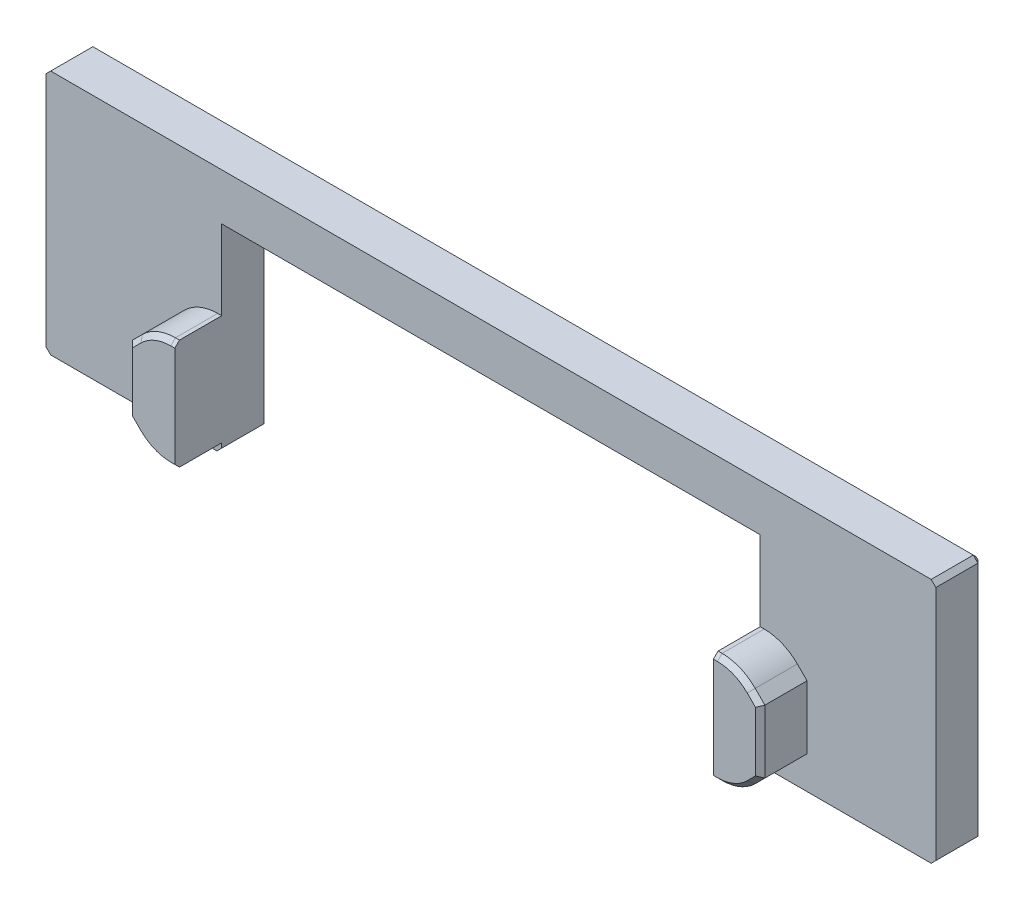
SolidWorks part; units mm, degrees
ref_plane "Front" through (0, 0, 0) normal (0, 0, 1) x (1, 0, 0)
ref_plane "Top" through (0, 0, 0) normal (0, 1, 0) x (1, 0, 0)
ref_plane "Right" through (0, 0, 0) normal (1, 0, 0) x (0, 0, -1)
sketch "Sketch1" plane through (0, 0, 0) normal (0, 0, 1) x (1, 0, 0)
  line L0 (-18.8, 5.25) -> (18.8, 5.25)
  line L5 (19, 5.05) -> (19, -5.05)
  line L6 (18.8, -5.25) -> (11.7, -5.25)
  line L7 (11.5, -5.05) -> (11.5, 3.25)
  line L8 (11.5, 3.25) -> (-11.5, 3.25)
  line L9 (-11.5, 3.25) -> (-11.5, -5.05)
  line L10 (-11.7, -5.25) -> (-18.8, -5.25)
  line L11 (-19, -5.05) -> (-19, 5.05)
  line L12 (19, 5.05) -> (19, -5.05) construction
  line L13 (18.8, -5.25) -> (11.7, -5.25) construction
  line L14 (18.8, 5.25) -> (-18.8, 5.25) construction
  line L15 (19, -5.05) -> (18.8, -5.25)
  line L16 (-11.7, -5.25) -> (-18.8, -5.25) construction
  line L17 (-19, 5.05) -> (-19, -5.05) construction
  line L18 (11.7, -5.25) -> (11.5, -5.05)
  line L19 (18.8, 5.25) -> (19, 5.05)
  line L20 (-19, 5.05) -> (-18.8, 5.25)
  line L21 (-18.8, -5.25) -> (-19, -5.05)
  line L22 (-11.5, -5.05) -> (-11.7, -5.25)
  point P0 (-19, 5.25)
  point P1 (19, 5.25)
  point P2 (19, -5.25)
  point P4 (11.5, -5.25)
  point P6 (-19, -5.25)
  point P13 (-11.5, -5.25)
extrude "Boss-Extrude1" add sketch "Sketch1" against normal blind 2
sketch "Sketch3" plane through (0, 0, 0) normal (0, 0, 1) x (1, 0, 0)
  line L3 (11.5, -5.05) -> (11.5, 3.25) construction
  line L4 (11.5, -4.85) -> (11.5, -0.15)
  line L20 (13.5, -3.85) -> (13.5, -1.15)
  line L21 (13.5, -3.85) -> (13.5, -1.15)
  line L22 (13.5, -1.15) -> (13.0858, -0.7358)
  line L23 (13.5, -1.15) -> (13.0858, -0.7358)
  line L24 (11.6716, -0.15) -> (10.8284, -0.15)
  line L25 (11.6716, -0.15) -> (11.5, -0.15)
  line L26 (9.4142, -0.7358) -> (9, -1.15)
  line L28 (9, -1.15) -> (9, -3.85)
  line L30 (9, -3.85) -> (9.4142, -4.2642)
  line L32 (10.8284, -4.85) -> (11.6716, -4.85)
  line L33 (11.5, -4.85) -> (11.6716, -4.85)
  line L34 (13.0858, -4.2642) -> (13.5, -3.85)
  line L35 (13.0858, -4.2642) -> (13.5, -3.85)
  arc A18 (13.0858, -0.7358) -> (11.6716, -0.15) centre (11.6716, -2.15) ccw
  arc A19 (13.0858, -0.7358) -> (11.6716, -0.15) centre (11.6716, -2.15) ccw
  arc A20 (10.8284, -0.15) -> (9.4142, -0.7358) centre (10.8284, -2.15) ccw
  arc A22 (9.4142, -4.2642) -> (10.8284, -4.85) centre (10.8284, -2.85) ccw
  arc A24 (11.6716, -4.85) -> (13.0858, -4.2642) centre (11.6716, -2.85) ccw
  arc A25 (11.6716, -4.85) -> (13.0858, -4.2642) centre (11.6716, -2.85) ccw
  line M20 (11.5, 3.25) -> (11.5, -5.05)
  dimension "D1" = 0
extrude "Boss-Extrude3" add sketch "Sketch3" along normal blind 2 contours L4 | L33 A25 L35 L21 L23 A19 L25 M20 region at (12.42, -2.5, 0)
mirror "Mirror3" about plane through (0, 0, 0) normal (1, 0, 0) of "Boss-Extrude3"
chamfer "Deburs" distance 0.2 angle 45 28 edges at (11.5, -0.9, -2) (11.6, -5.15, -2) (15.25, -5.25, -2) (18.9, -5.15, -2) (19, 0, -2) (18.9, 5.15, -2) (0, 5.25, -2) (-18.9, 5.15, -2) (-19, 0, -2) (-18.9, -5.15, -2) (-15.25, -5.25, -2) (-11.6, -5.15, -2) (-11.5, -0.9, -2) (0, 3.25, -2) (-11.5858, -4.85, 2) (-13.2929, -4.0571, 2) (-12.4369, -4.6978, 2) (-13.5, -2.5, 2) (-13.2929, -0.9429, 2) (-11.5858, -0.15, 2) (-12.4369, -0.3022, 2) (11.5858, -4.85, 2) (13.2929, -4.0571, 2) (12.4369, -4.6978, 2) (13.5, -2.5, 2) (13.2929, -0.9429, 2) (11.5858, -0.15, 2) (12.4369, -0.3022, 2)
